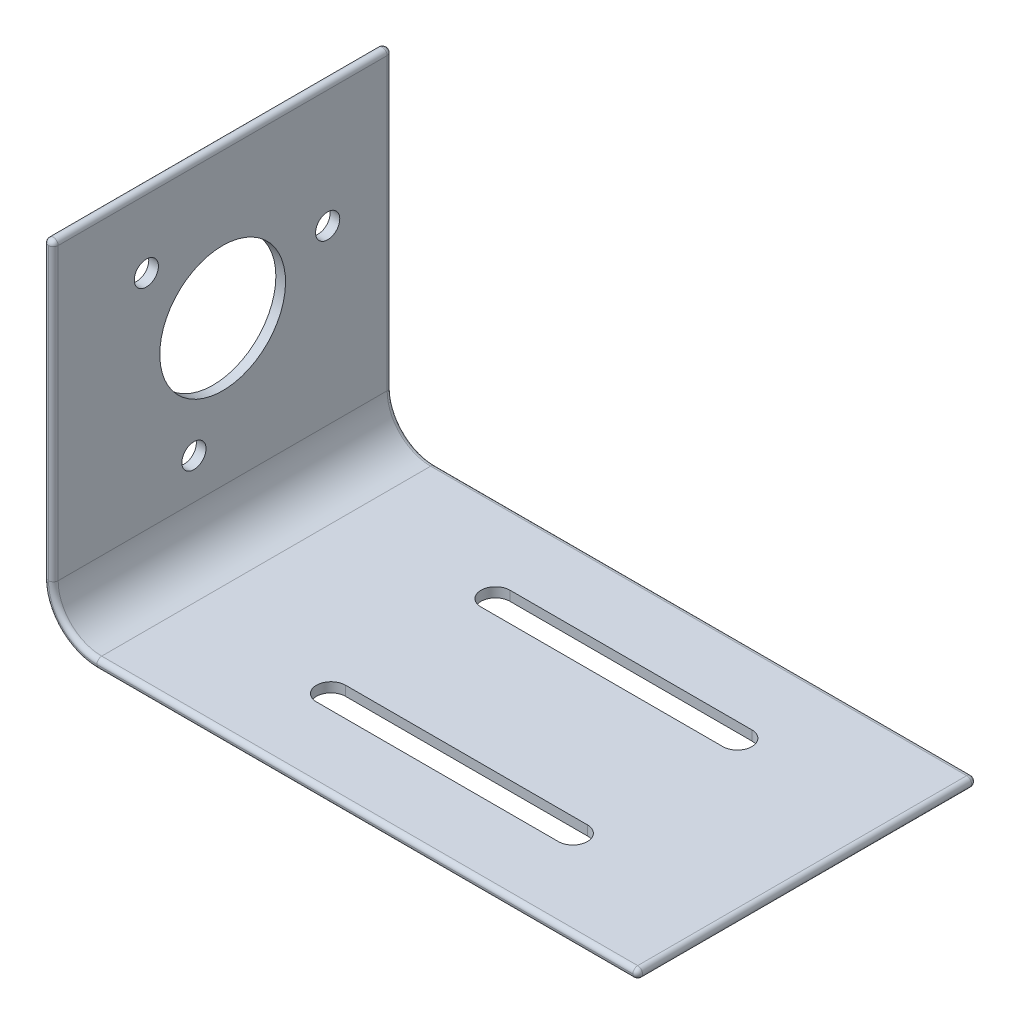
SolidWorks part; units mm, degrees
ref_plane "Front Plane" through (0, 0, 0) normal (0, 0, 1) x (1, 0, 0)
ref_plane "Top Plane" through (0, 0, 0) normal (0, 1, 0) x (1, 0, 0)
ref_plane "Right Plane" through (0, 0, 0) normal (1, 0, 0) x (0, 0, -1)
sketch "Sketch1" plane through (0, 0, 0) normal (0, 0, 1) x (1, 0, 0)
  line L0 (0, 0) -> (-55.4, 0)
  line L1 (-60.4, 5) -> (-60.4, 35) construction
  line L3 (0, 0.5) -> (-55.4, 0.5)
  line L4 (-59.9, 5) -> (-59.9, 35)
  line L5 (0, -0.5) -> (-55.4, -0.5)
  line L6 (-60.9, 5) -> (-60.9, 35)
  arc A0 (-55.4, 0) -> (-60.4, 5) centre (-55.4, 5) cw
  arc A1 (-55.4, 0.5) -> (-59.9, 5) centre (-55.4, 5) cw
  arc A2 (-55.4, -0.5) -> (-60.9, 5) centre (-55.4, 5) cw
  arc A3 (0, 0.5) -> (0, -0.5) centre (0, 0) cw
  arc A4 (-59.9, 35) -> (-60.9, 35) centre (-60.4, 35) ccw
  point P6 (-60.4, 0)
  point P17 (-60.4, 20)
  dimension "D3" = 5
  dimension "D1" = 35
  dimension "D2" = 60.4
  dimension "D4" = 0.5
  dimension "D5" = 0.5
extrude "Boss-Extrude1" add sketch "Sketch1" along normal blind 35 contours L4 A4 L6 A2 L5 A3 L3 A1
sketch "Sketch3" plane through (-59.9, 0, 0) normal (1, 0, 0) x (0, 0, -1)
  line L0 (-17.5, 35) -> (-17.5, 5) construction
  line L1 (-35, 35) -> (0, 35) construction
  line L2 (-35, 5) -> (0, 5) construction
  circle A0 centre (-17.5, 20) radius 6.5
  circle A1 centre (-17.5, 20) radius 10.5 construction
  point P9 (-27.8184, 21.9445)
  point P13 (-10.6569, 27.9638)
  point P14 (-14.0248, 10.0918)
  point P15 (-17.5, 20)
  dimension "D1" = 13
  dimension "D2" = 21
  dimension "D3" = 3
extrude "Cut-Extrude1" cut sketch "Sketch3" against normal up to body separate body contours A0
fillet "Fillet1" radius 0.5 16 edges at (-59.9, 20, 0) (-60.4, 35.5, 0) (-60.9, 20, 0) (-59.2891, 1.1109, 0) (-27.7, -0.5, 0) (-27.7, 0.5, 0) (-58.582, 1.818, 0) (0.5, 0, 0) (-27.7, 0.5, 35) (0.5, 0, 35) (-27.7, -0.5, 35) (-59.2891, 1.1109, 35) (-60.9, 20, 35) (-60.4, 35.5, 35) (-59.9, 20, 35) (-58.582, 1.818, 35)
sketch "Sketch6" plane through (0, 0.5, 0) normal (0, 1, 0) x (1, 0, 0)
  line L0 (0, -17.5) -> (-55.4, -17.5) construction
  line L1 (0, -34.5) -> (0, -0.5) construction
  line L2 (-55.4, -34.5) -> (-55.4, -0.5) construction
  line L3 (-27.7, -0.5) -> (-27.7, -17.5) construction
  line L4 (0, -0.5) -> (-55.4, -0.5) construction
  line L6 (-40.2, -9) -> (-15.2, -9) construction
  line L7 (-40.2, -7.5) -> (-15.2, -7.5)
  line L8 (-40.2, -10.5) -> (-15.2, -10.5)
  line L9 (-40.2, -26) -> (-15.2, -26) construction
  line L10 (-40.2, -27.5) -> (-15.2, -27.5)
  line L11 (-40.2, -24.5) -> (-15.2, -24.5)
  arc A0 (-40.2, -7.5) -> (-40.2, -10.5) centre (-40.2, -9) ccw
  arc A1 (-15.2, -10.5) -> (-15.2, -7.5) centre (-15.2, -9) ccw
  arc A2 (-40.2, -27.5) -> (-40.2, -24.5) centre (-40.2, -26) cw
  arc A3 (-15.2, -24.5) -> (-15.2, -27.5) centre (-15.2, -26) cw
  point P14 (-27.7, -9)
  point P25 (-27.7, -26)
  dimension "D2" = 1.5
  dimension "D1" = 25
extrude "Cut-Extrude3" cut sketch "Sketch6" against normal blind 35 contours L8 A1 L7 A0 | L10 A3 L11 A2
sketch "Sketch7" plane through (-59.9, 0, 0) normal (1, 0, 0) x (0, 0, -1)
  circle A0 centre (-17.5, 20) radius 11.22
  point P3 (-25.3858, 27.9814)
  point P7 (-20.4692, 9.18)
  point P8 (-6.645, 22.8386)
  point P9 (-17.5, 20)
  dimension "D1" = 22.44
  dimension "D2" = 3
hole_wizard "Ø2.5mm Dowel Hole1" positions "3DSketch3" profile "Sketch8" hole size "Ø2.5" standard "ANSI Metric" end condition through all
sketch3d "3DSketch3"
  point P0 (-59.9, 27.9814, 25.3858)
  point P3 (-59.9, 9.18, 20.4692)
  point P6 (-59.9, 22.8386, 6.645)
sketch "Sketch8" plane through (-59.9, 27.9814, 25.3858) normal (0, 1, 0) x (0, 0, -1)
  line L0 (0, 0) -> (0, 1)
  line L1 (0, 1) -> (1.25, 1)
  line L2 (1.25, 1) -> (1.25, 0)
  line L5 (1.25, 0) -> (0, 0)
  line L11 (0, -6.35) -> (0, 107.95) construction
  dimension "Thru Hole Dia." = 2.5
  dimension "Thru Hole Depth" = 1
